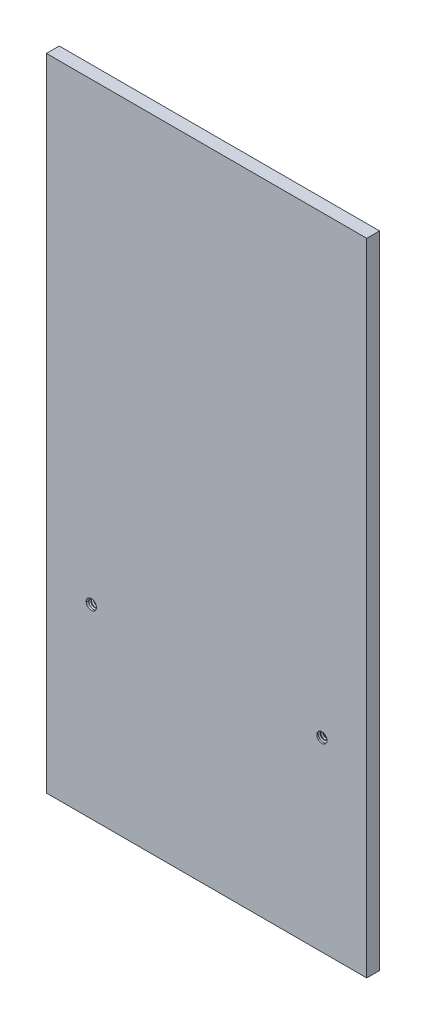
SolidWorks part; units mm, degrees
ref_plane "Front Plane" through (0, 0, 0) normal (0, 0, 1) x (1, 0, 0)
ref_plane "Top Plane" through (0, 0, 0) normal (0, 1, 0) x (1, 0, 0)
ref_plane "Right Plane" through (0, 0, 0) normal (1, 0, 0) x (0, 0, -1)
sketch "Sketch1" plane through (0, 0, 0) normal (0, 0, 1) x (1, 0, 0)
  line L1 (-25, -50) -> (25, -50)
  line L2 (-25, -50) -> (-25, 50)
  line L3 (-25, 50) -> (25, 50)
  line L4 (25, -50) -> (25, 50)
  line L5 (-25, -50) -> (25, 50) construction
  line L6 (-25, 50) -> (25, -50) construction
  point P0 (0, 0)
  dimension "D1" = 50
  dimension "D2" = 100
extrude "Boss-Extrude1" add sketch "Sketch1" along normal blind 2
hole_wizard "M2 Tapped Hole1" positions "Sketch4" profile "Sketch5" tap size "M2" standard "ISO" end condition through all
sketch "Sketch4" plane through (0, 0, 2) normal (0, 0, 1) x (1, 0, 0)
  line L0 (0, -1.1) -> (0, 1.1) construction
  line L1 (-25, -50) -> (25, -50) construction
  point P0 (18, -21)
  point P2 (-18, -21)
  dimension "D1" = 18
  dimension "D2" = 18
  dimension "D3" = 29
  dimension "D4" = 29
sketch "Sketch5" plane through (18, -21, 2) normal (1, 0, 0) x (0, -1, 0)
  line L0 (0, 0) -> (0, 2)
  line L1 (0, 2) -> (0.8, 2)
  line L2 (0.8, 2) -> (0.8, 0)
  line L5 (0.8, 0) -> (0, 0)
  line L11 (0, -6.35) -> (0, 107.95) construction
  dimension "Thru Tap Drill Dia." = 1.6
  dimension "Thru Tap Drill Depth" = 2
cosmetic thread "Hole Thread1" parameters "D2"=2
cosmetic thread "Hole Thread2" parameters "D2"=2
thread "Thread1" pitch 0.4 method extrude profile "Thread Profile1" start angle 0, offset 0, length 1.6, pitch 0.4, diameter 1.6
ref_plane "Plane1" through (-18.8, -21, 2) normal (0, -1, 0) x (-1, 0, 0)
sketch "Thread Profile1" plane through (-18.8, -21, 2) normal (0, -1, 0) x (-1, 0, 0)
  line L0 (0, 0) -> (0, 0.4) construction
  line L11 (0, 0) -> (0, 0.35)
  line L12 (0, 0.35) -> (-0.2165, 0.225)
  line L13 (-0.2165, 0.225) -> (-0.2165, 0.125)
  line L15 (-0.2165, 0.125) -> (0, 0)
  line L17 (-0.2165, 0.175) -> (0, 0.175) construction
  point P2 (0, 0)
  dimension "Pitch" = 0.4
  dimension "Profile_Angle" = 60
  dimension "Profile_Land" = 0.1
  dimension "Profile_Height" = 0.2165
mirror "Mirror3" about plane through (0, 0, 0) normal (1, 0, 0) of "Thread1"
